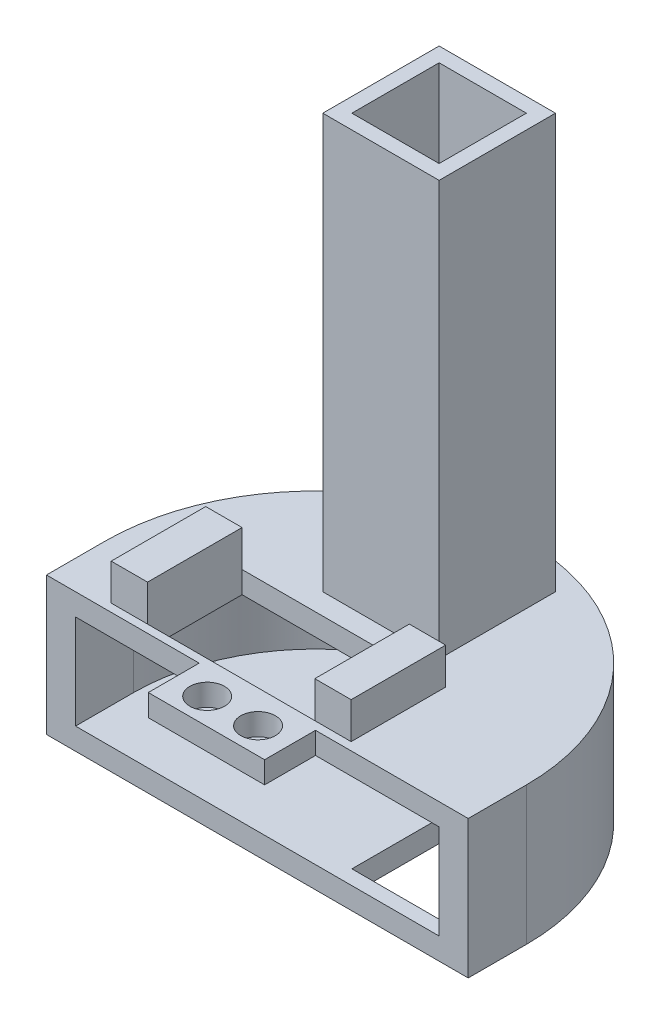
SolidWorks part; units mm, degrees
ref_plane "Front Plane" through (0, 0, 0) normal (0, 0, 1) x (1, 0, 0)
ref_plane "Top Plane" through (0, 0, 0) normal (0, 1, 0) x (1, 0, 0)
ref_plane "Right Plane" through (0, 0, 0) normal (1, 0, 0) x (0, 0, -1)
sketch "Sketch2" plane through (0, 0, 0) normal (0, 1, 0) x (1, 0, 0)
  line L0 (25, 0) -> (-25, 0)
  line L1 (0, 8) -> (0, 33) construction
  line L2 (25, 0) -> (25, 8)
  line L3 (-25, 0) -> (-25, 8)
  line L4 (-29, 0) -> (29, 0)
  line L5 (0, 33) -> (0, 37) construction
  line L6 (6, 19) -> (-6, 19)
  line L7 (6, 19) -> (6, 31)
  line L8 (6, 31) -> (-6, 31)
  line L9 (-6, 19) -> (-6, 31)
  line L10 (6, 19) -> (-6, 31) construction
  line L11 (6, 31) -> (-6, 19) construction
  line L12 (-29, 0) -> (-29, 8)
  line L13 (23, 2) -> (11, 2)
  line L14 (23, 2) -> (23, 14)
  line L15 (23, 14) -> (11, 14)
  line L16 (11, 2) -> (11, 14)
  line L17 (23, 2) -> (11, 14) construction
  line L18 (23, 14) -> (11, 2) construction
  line L19 (29, 0) -> (29, 8)
  arc A0 (-25, 8) -> (25, 8) centre (0, 8) cw
  arc A1 (-29, 8) -> (29, 8) centre (0, 8) cw
  point P8 (0, 25)
  point P15 (17, 8)
  point P21 (0, 0)
  dimension "D1" = 58
  dimension "D2" = 25
  dimension "D3" = 4
  dimension "D4" = 17
  dimension "D5" = 12
  dimension "D6" = 12
  dimension "D7" = 17
  dimension "D8" = 12
  dimension "D9" = 12
extrude "Boss-Extrude1" add sketch "Sketch2" along normal blind 16 contours A1 L12 L4 L3 A0 L2 L19 region at (25.688, 0, -4)
extrude "Boss-Extrude2" add sketch "Sketch2<5>" along normal blind 3 contours A0 L3 L0 L2 L6 L9 L8 L7 L13 L16 L15 L14 | L9 L6 L7 L8 region at (-2.2382, 0, -13.8228) region at (0, 0, -25)
sketch "Sketch2<5>" plane through (0, 0, 0) normal (0, 1, 0) x (1, 0, 0) same geometry as "Sketch2"
sketch "Sketch3" plane through (0, 16, 0) normal (0, 1, 0) x (1, 0, 0)
  line L0 (-29, 0) -> (-25, 0)
  line L2 (-29, 0) -> (-29, 8)
  line L4 (25, 0) -> (29, 0)
  line L5 (29, 0) -> (29, 8)
  line L6 (-25, 0) -> (25, 0)
  line L7 (-6, 31) -> (6, 31)
  line L8 (-6, 31) -> (-6, 19)
  line L9 (-6, 19) -> (6, 19)
  line L10 (6, 31) -> (6, 19)
  line L11 (8, 17) -> (-8, 17)
  line L12 (8, 17) -> (8, 33)
  line L13 (8, 33) -> (-8, 33)
  line L14 (-8, 17) -> (-8, 33)
  line L15 (8, 17) -> (-8, 33) construction
  line L16 (8, 33) -> (-8, 17) construction
  line L17 (0, 8) -> (9, 8) construction
  line L18 (9, 1.5) -> (9, 14.5)
  line L19 (0, 8) -> (-14, 8) construction
  line L20 (-14, 1.5) -> (-14, 14.5) construction
  line L21 (-16.2, 14.1) -> (6.8, 14.1)
  line L22 (-16.2, 1.1) -> (6.8, 1.1)
  line L23 (-14, 8) -> (-19, 8) construction
  line L24 (9, 8) -> (14, 8) construction
  line L25 (-2.5, 8) -> (-2.5, 4.0917) construction
  line L26 (-21.2, 1.1) -> (-16.2, 1.1)
  line L27 (-21.2, 1.1) -> (-21.2, 14.1)
  line L28 (-21.2, 14.1) -> (-16.2, 14.1)
  line L29 (-16.2, 1.1) -> (-16.2, 14.1)
  line L30 (-19, 1.5) -> (-14, 14.5) construction
  line L31 (-19, 14.5) -> (-14, 1.5) construction
  line L32 (11.8, 1.1) -> (6.8, 1.1)
  line L33 (11.8, 1.1) -> (11.8, 14.1)
  line L34 (11.8, 14.1) -> (6.8, 14.1)
  line L35 (6.8, 1.1) -> (6.8, 14.1)
  line L36 (14, 1.5) -> (9, 14.5) construction
  line L37 (14, 14.5) -> (9, 1.5) construction
  line L38 (0, -7) -> (0, 0) construction
  line L39 (8, -7) -> (-8, -7)
  line L40 (8, -7) -> (8, 0)
  line L41 (8, 0) -> (-8, 0)
  line L42 (-8, -7) -> (-8, 0)
  line L43 (8, -7) -> (-8, 0) construction
  line L44 (8, 0) -> (-8, -7) construction
  arc A1 (-29, 8) -> (29, 8) centre (0, 8) cw
  circle A2 centre (0, 8) radius 2.5
  circle A3 centre (-3.5, -3.4) radius 2.3813
  circle A4 centre (3.5, -3.4) radius 2.3812
  point P5 (-16.5, 8)
  point P24 (0, 25)
  point P31 (9, 8)
  point P34 (-14, 8)
  point P37 (11.5, 8)
  point P52 (0, -3.5)
  point P64 (0, 0)
  point P65 (0, 0)
  point P66 (0, 0)
  point P67 (0, 0)
  arc M3 (29, 8) -> (-29, 8) centre (0, 8) ccw
  line M4 (-29, 8) -> (-29, 0)
  line M5 (-29, 0) -> (-25, 0)
  line M6 (-25, 0) -> (-25, 8)
  arc M7 (-25, 8) -> (25, 8) centre (0, 8) cw
  line M8 (25, 8) -> (25, 0)
  line M9 (25, 0) -> (29, 0)
  line M10 (29, 0) -> (29, 8)
  dimension "D3" = 5
  dimension "D9" = 4.7625
  dimension "D1" = 16
  dimension "D2" = 16
  dimension "D4" = 9
  dimension "D5" = 13
  dimension "D6" = 14
  dimension "D7" = 5
  dimension "D8" = 5
  dimension "D10" = 16
  dimension "D11" = 7
  dimension "D12" = 4.5
  dimension "D13" = 7
extrude "Boss-Extrude3" add sketch "Sketch3" along normal blind 3 contours L14 L13 L12 M7 M8 M9 M10 M3 M4 M5 M6 | L11 L14 L6 L12 M7 M6 M8 | L10 L7 L8 L9 | L14 L13 L12 L11 | L27 L26 L29 L28 | L33 L32 L35 L34 | L40 L39 L42 L41 | A3 | A4 region at (-28.312, 16, -4) region at (2.8654, 16, -14.8311) region at (0, 16, -25)
extrude "Boss-Extrude4" add sketch "Sketch3<4>" along normal blind 60 contours L10 L7 L8 L9 | L12 L13 L14 L11 region at (0, 16, -25)
sketch "Sketch3<4>" plane through (0, 16, 0) normal (0, 1, 0) x (1, 0, 0) same geometry as "Sketch3"
extrude "Boss-Extrude5" add sketch "Sketch3<5>" along normal blind 8 contours L26 L29 L28 L27 | L33 L34 L18 L32 region at (-18.7, 16, -7.6) region at (9.3, 16, -7.6)
sketch "Sketch3<5>" plane through (0, 16, 0) normal (0, 1, 0) x (1, 0, 0) same geometry as "Sketch3"
